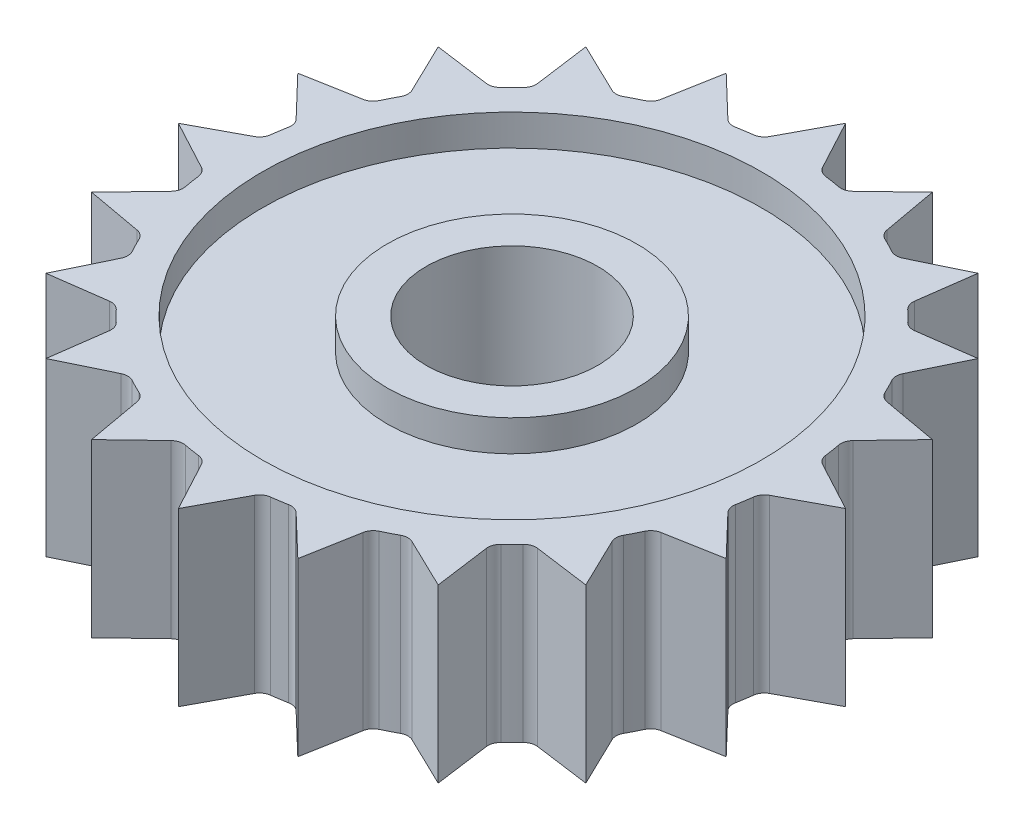
SolidWorks part; units mm, degrees
material "PET"
ref_plane "Front Plane" through (0, 0, 0) normal (0, 0, 1) x (1, 0, 0)
ref_plane "Top Plane" through (0, 0, 0) normal (0, 1, 0) x (1, 0, 0)
ref_plane "Right Plane" through (0, 0, 0) normal (1, 0, 0) x (0, 0, -1)
sketch "Sketch1" plane through (0, 0, 0) normal (0, 1, 0) x (1, 0, 0)
  line L0 (0, 0) -> (0, 13.5) construction
  line L1 (0, 13.5) -> (0, -14.5926) construction
  line L2 (0, 0) -> (13.5, 0) construction
  line L3 (13.5, 0) -> (-13.7634, 0) construction
  line L4 (0, 10.69) -> (-0.8515, 9.1032)
  line L5 (0, 10.69) -> (0.8515, 9.1032)
  line L8 (3.3034, 10.1668) -> (2.0033, 8.9208)
  line L9 (3.3034, 10.1668) -> (3.6228, 8.3946)
  line L10 (6.2834, 8.6484) -> (4.6619, 7.8651)
  line L11 (6.2834, 8.6484) -> (6.0396, 6.8642)
  line L12 (8.6484, 6.2834) -> (6.8642, 6.0396)
  line L13 (8.6484, 6.2834) -> (7.8651, 4.6619)
  line L14 (10.1668, 3.3034) -> (8.3946, 3.6228)
  line L15 (10.1668, 3.3034) -> (8.9208, 2.0033)
  line L16 (10.69, 0) -> (9.1032, 0.8515)
  line L17 (10.69, 0) -> (9.1032, -0.8515)
  line L18 (10.1668, -3.3034) -> (8.9208, -2.0033)
  line L19 (10.1668, -3.3034) -> (8.3946, -3.6228)
  line L20 (8.6484, -6.2834) -> (7.8651, -4.6619)
  line L21 (8.6484, -6.2834) -> (6.8642, -6.0396)
  line L22 (6.2834, -8.6484) -> (6.0396, -6.8642)
  line L23 (6.2834, -8.6484) -> (4.6619, -7.8651)
  line L24 (3.3034, -10.1668) -> (3.6228, -8.3946)
  line L25 (3.3034, -10.1668) -> (2.0033, -8.9208)
  line L26 (0, -10.69) -> (0.8515, -9.1032)
  line L27 (0, -10.69) -> (-0.8515, -9.1032)
  line L28 (-3.3034, -10.1668) -> (-2.0033, -8.9208)
  line L29 (-3.3034, -10.1668) -> (-3.6228, -8.3946)
  line L30 (-6.2834, -8.6484) -> (-4.6619, -7.8651)
  line L31 (-6.2834, -8.6484) -> (-6.0396, -6.8642)
  line L32 (-8.6484, -6.2834) -> (-6.8642, -6.0396)
  line L33 (-8.6484, -6.2834) -> (-7.8651, -4.6619)
  line L34 (-10.1668, -3.3034) -> (-8.3946, -3.6228)
  line L35 (-10.1668, -3.3034) -> (-8.9208, -2.0033)
  line L36 (-10.69, 0) -> (-9.1032, -0.8515)
  line L37 (-10.69, 0) -> (-9.1032, 0.8515)
  line L38 (-10.1668, 3.3034) -> (-8.9208, 2.0033)
  line L39 (-10.1668, 3.3034) -> (-8.3946, 3.6228)
  line L40 (-8.6484, 6.2834) -> (-7.8651, 4.6619)
  line L41 (-8.6484, 6.2834) -> (-6.8642, 6.0396)
  line L42 (-6.2834, 8.6484) -> (-6.0396, 6.8642)
  line L43 (-6.2834, 8.6484) -> (-4.6619, 7.8651)
  line L44 (-3.3034, 10.1668) -> (-3.6228, 8.3946)
  line L45 (-3.3034, 10.1668) -> (-2.0033, 8.9208)
  arc A0 (-1.1525, 8.8957) -> (-1.6528, 8.8164) centre (0, 0) ccw
  circle A1 centre (0, 0) radius 10.69 construction
  arc A2 (0.8515, 9.1032) -> (1.1525, 8.8957) centre (1.2039, 9.2923) ccw
  arc A3 (-0.8515, 9.1032) -> (-1.1525, 8.8957) centre (-1.2039, 9.2923) cw
  arc A4 (3.6228, 8.3946) -> (3.845, 8.1041) centre (4.0165, 8.4655) ccw
  arc A5 (2.0033, 8.9208) -> (1.6528, 8.8164) centre (1.7265, 9.2096) cw
  arc A6 (6.0396, 6.8642) -> (6.1611, 6.5193) centre (6.4359, 6.81) ccw
  arc A7 (4.6619, 7.8651) -> (4.2963, 7.8742) centre (4.4879, 8.2253) cw
  arc A8 (7.8651, 4.6619) -> (7.8742, 4.2963) centre (8.2253, 4.4879) ccw
  arc A9 (6.8642, 6.0396) -> (6.5193, 6.1611) centre (6.81, 6.4359) cw
  arc A10 (8.9208, 2.0033) -> (8.8164, 1.6528) centre (9.2096, 1.7265) ccw
  arc A11 (8.3946, 3.6228) -> (8.1041, 3.845) centre (8.4655, 4.0165) cw
  arc A12 (9.1032, -0.8515) -> (8.8957, -1.1525) centre (9.2923, -1.2039) ccw
  arc A13 (9.1032, 0.8515) -> (8.8957, 1.1525) centre (9.2923, 1.2039) cw
  arc A14 (8.3946, -3.6228) -> (8.1041, -3.845) centre (8.4655, -4.0165) ccw
  arc A15 (8.9208, -2.0033) -> (8.8164, -1.6528) centre (9.2096, -1.7265) cw
  arc A16 (6.8642, -6.0396) -> (6.5193, -6.1611) centre (6.81, -6.4359) ccw
  arc A17 (7.8651, -4.6619) -> (7.8742, -4.2963) centre (8.2253, -4.4879) cw
  arc A18 (4.6619, -7.8651) -> (4.2963, -7.8742) centre (4.4879, -8.2253) ccw
  arc A19 (6.0396, -6.8642) -> (6.1611, -6.5193) centre (6.4359, -6.81) cw
  arc A20 (2.0033, -8.9208) -> (1.6528, -8.8164) centre (1.7265, -9.2096) ccw
  arc A21 (3.6228, -8.3946) -> (3.845, -8.1041) centre (4.0165, -8.4655) cw
  arc A22 (-0.8515, -9.1032) -> (-1.1525, -8.8957) centre (-1.2039, -9.2923) ccw
  arc A23 (0.8515, -9.1032) -> (1.1525, -8.8957) centre (1.2039, -9.2923) cw
  arc A24 (-3.6228, -8.3946) -> (-3.845, -8.1041) centre (-4.0165, -8.4655) ccw
  arc A25 (-2.0033, -8.9208) -> (-1.6528, -8.8164) centre (-1.7265, -9.2096) cw
  arc A26 (-6.0396, -6.8642) -> (-6.1611, -6.5193) centre (-6.4359, -6.81) ccw
  arc A27 (-4.6619, -7.8651) -> (-4.2963, -7.8742) centre (-4.4879, -8.2253) cw
  arc A28 (-7.8651, -4.6619) -> (-7.8742, -4.2963) centre (-8.2253, -4.4879) ccw
  arc A29 (-6.8642, -6.0396) -> (-6.5193, -6.1611) centre (-6.81, -6.4359) cw
  arc A30 (-8.9208, -2.0033) -> (-8.8164, -1.6528) centre (-9.2096, -1.7265) ccw
  arc A31 (-8.3946, -3.6228) -> (-8.1041, -3.845) centre (-8.4655, -4.0165) cw
  arc A32 (-9.1032, 0.8515) -> (-8.8957, 1.1525) centre (-9.2923, 1.2039) ccw
  arc A33 (-9.1032, -0.8515) -> (-8.8957, -1.1525) centre (-9.2923, -1.2039) cw
  arc A34 (-8.3946, 3.6228) -> (-8.1041, 3.845) centre (-8.4655, 4.0165) ccw
  arc A35 (-8.9208, 2.0033) -> (-8.8164, 1.6528) centre (-9.2096, 1.7265) cw
  arc A36 (-6.8642, 6.0396) -> (-6.5193, 6.1611) centre (-6.81, 6.4359) ccw
  arc A37 (-7.8651, 4.6619) -> (-7.8742, 4.2963) centre (-8.2253, 4.4879) cw
  arc A38 (-4.6619, 7.8651) -> (-4.2963, 7.8742) centre (-4.4879, 8.2253) ccw
  arc A39 (-6.0396, 6.8642) -> (-6.1611, 6.5193) centre (-6.4359, 6.81) cw
  arc A40 (-2.0033, 8.9208) -> (-1.6528, 8.8164) centre (-1.7265, 9.2096) ccw
  arc A41 (-3.6228, 8.3946) -> (-3.845, 8.1041) centre (-4.0165, 8.4655) cw
  arc A42 (-3.845, 8.1041) -> (-4.2963, 7.8742) centre (0, 0) ccw
  arc A43 (-6.1611, 6.5193) -> (-6.5193, 6.1611) centre (0, 0) ccw
  arc A44 (-7.8742, 4.2963) -> (-8.1041, 3.845) centre (0, 0) ccw
  arc A45 (-8.8164, 1.6528) -> (-8.8957, 1.1525) centre (0, 0) ccw
  arc A46 (-8.8957, -1.1525) -> (-8.8164, -1.6528) centre (0, 0) ccw
  arc A47 (-8.1041, -3.845) -> (-7.8742, -4.2963) centre (0, 0) ccw
  arc A48 (-6.5193, -6.1611) -> (-6.1611, -6.5193) centre (0, 0) ccw
  arc A49 (-4.2963, -7.8742) -> (-3.845, -8.1041) centre (0, 0) ccw
  arc A50 (-1.6528, -8.8164) -> (-1.1525, -8.8957) centre (0, 0) ccw
  arc A51 (1.1525, -8.8957) -> (1.6528, -8.8164) centre (0, 0) ccw
  arc A52 (3.845, -8.1041) -> (4.2963, -7.8742) centre (0, 0) ccw
  arc A53 (6.1611, -6.5193) -> (6.5193, -6.1611) centre (0, 0) ccw
  arc A54 (7.8742, -4.2963) -> (8.1041, -3.845) centre (0, 0) ccw
  arc A55 (8.8164, -1.6528) -> (8.8957, -1.1525) centre (0, 0) ccw
  arc A56 (8.8957, 1.1525) -> (8.8164, 1.6528) centre (0, 0) ccw
  arc A57 (8.1041, 3.845) -> (7.8742, 4.2963) centre (0, 0) ccw
  arc A58 (6.5193, 6.1611) -> (6.1611, 6.5193) centre (0, 0) ccw
  arc A59 (4.2963, 7.8742) -> (3.845, 8.1041) centre (0, 0) ccw
  arc A60 (1.6528, 8.8164) -> (1.1525, 8.8957) centre (0, 0) ccw
  point P12 (0.95, 8.9196)
  point P15 (-0.95, 8.9196)
  point P152 (0, 0)
  dimension "D1" = 21.38
  dimension "D2" = 17.94
  dimension "D6" = 0.4
  dimension "D3" = 13.5
  dimension "D4" = 1.9
  dimension "D5" = 28.217
  dimension "D7" = 20
extrude "Boss-Extrude1" add sketch "Sketch1" along normal blind 5.5
sketch "Sketch2" plane through (0, 5.5, 0) normal (0, 1, 0) x (1, 0, 0)
  circle A0 centre (0, 0) radius 2.75
  circle A1 centre (0, 0) radius 4
  circle A2 centre (0, 0) radius 8
  dimension "D1" = 16
  dimension "D2" = 8
  dimension "D3" = 5.5
extrude "Cut-Extrude1" cut sketch "Sketch2" against normal through all contours A0 region at (0, 5.5, 0)
extrude "Cut-Extrude2" cut sketch "Sketch2<3>" against normal blind 1 contours A2 A1 region at (-7.7737, 5.5, 0)
sketch "Sketch2<3>" plane through (0, 5.5, 0) normal (0, 1, 0) x (1, 0, 0) same geometry as "Sketch2"
sketch "Sketch3" plane through (0, 0, 0) normal (0, -1, 0) x (1, 0, 0)
  circle A0 centre (0, 0) radius 4
  circle A1 centre (0, 0) radius 8
  dimension "D1" = 16
  dimension "D2" = 8
extrude "Cut-Extrude3" cut sketch "Sketch3" against normal blind 1
sketch "Sketch4" plane through (0, 0, 0) normal (0, -1, 0) x (1, 0, 0)
  circle A0 centre (0, 0) radius 10
  dimension "D1" = 20
